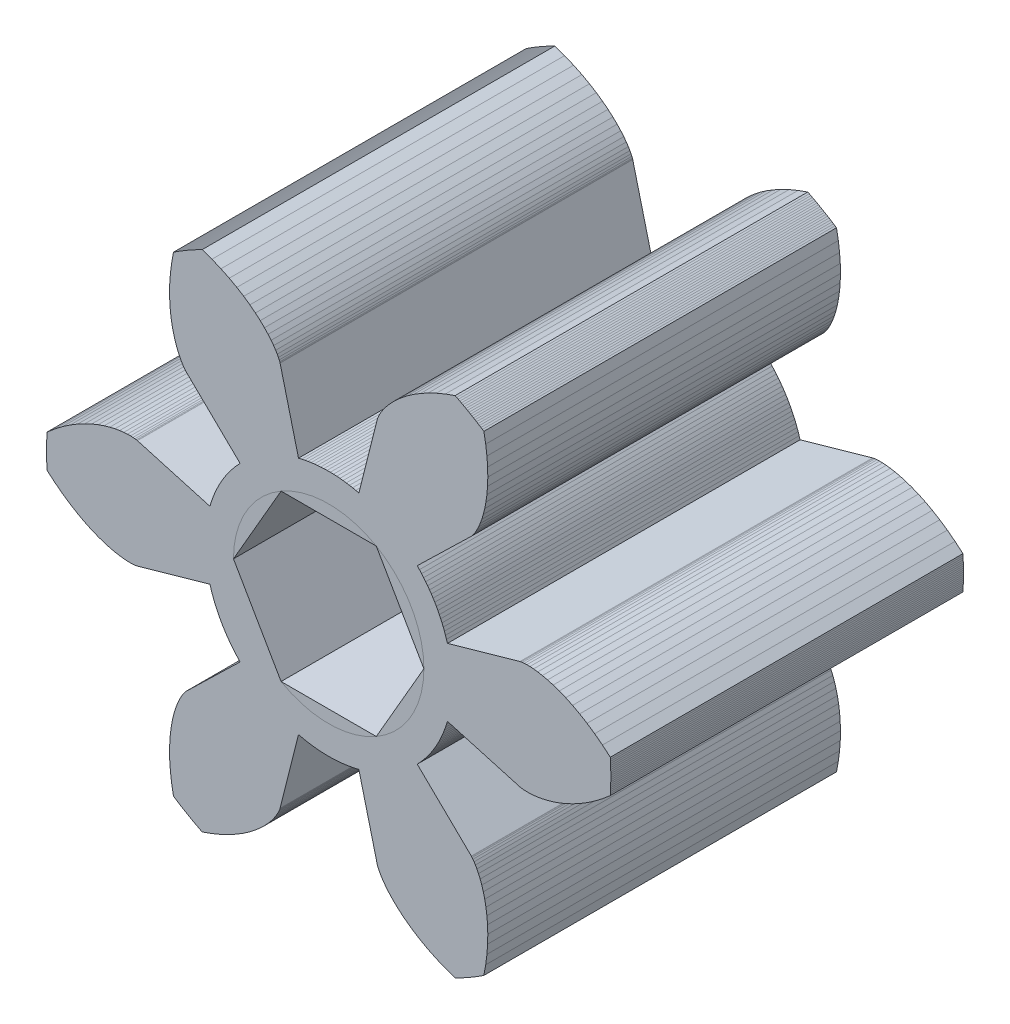
SolidWorks part; units mm, degrees
ref_plane "Front Plane" through (0, 0, 0) normal (0, 0, 1) x (1, 0, 0)
ref_plane "Top Plane" through (0, 0, 0) normal (0, 1, 0) x (1, 0, 0)
ref_plane "Right Plane" through (0, 0, 0) normal (1, 0, 0) x (0, 0, -1)
sketch "Model" plane through (0, 0, 0) normal (0, 0, 1) x (1, 0, 0)
  line L0 (3.3669, -0.9562) -> (5.4237, -1.5403)
  line L1 (5.4237, -1.5403) -> (5.4314, -1.5422)
  line L2 (5.4314, -1.5422) -> (5.4547, -1.5467)
  line L3 (5.4547, -1.5467) -> (5.4938, -1.5524)
  line L4 (5.4938, -1.5524) -> (5.549, -1.5573)
  line L5 (5.549, -1.5573) -> (5.6201, -1.56)
  line L6 (5.6201, -1.56) -> (5.7072, -1.5586)
  line L7 (5.7072, -1.5586) -> (5.8098, -1.5516)
  line L8 (5.8098, -1.5516) -> (5.9276, -1.5373)
  line L9 (5.9276, -1.5373) -> (6.06, -1.514)
  line L10 (6.06, -1.514) -> (6.2065, -1.4801)
  line L11 (6.2065, -1.4801) -> (6.3662, -1.4342)
  line L12 (6.3662, -1.4342) -> (6.5382, -1.3747)
  line L13 (6.5382, -1.3747) -> (6.7214, -1.3003)
  line L14 (6.7214, -1.3003) -> (6.9148, -1.2095)
  line L15 (6.9148, -1.2095) -> (7.1171, -1.1012)
  line L16 (7.1171, -1.1012) -> (7.3268, -0.9741)
  line L17 (7.3268, -0.9741) -> (7.5426, -0.8271)
  line L18 (7.5426, -0.8271) -> (7.763, -0.6594)
  line L19 (7.763, -0.6594) -> (7.9862, -0.47)
  line L20 (7.9862, -0.47) -> (7.9889, -0.4205)
  line L21 (7.9889, -0.4205) -> (7.9914, -0.3711)
  line L22 (7.9914, -0.3711) -> (7.9935, -0.3217)
  line L23 (7.9935, -0.3217) -> (7.9954, -0.2722)
  line L24 (7.9954, -0.2722) -> (7.9969, -0.2227)
  line L25 (7.9969, -0.2227) -> (7.9981, -0.1732)
  line L26 (7.9981, -0.1732) -> (7.999, -0.1237)
  line L27 (7.999, -0.1237) -> (7.9997, -0.0742)
  line L28 (7.9997, -0.0742) -> (8, -0.0247)
  line L29 (8, -0.0247) -> (8, 0.0247)
  line L30 (8, 0.0247) -> (7.9997, 0.0742)
  line L31 (7.9997, 0.0742) -> (7.999, 0.1237)
  line L32 (7.999, 0.1237) -> (7.9981, 0.1732)
  line L33 (7.9981, 0.1732) -> (7.9969, 0.2227)
  line L34 (7.9969, 0.2227) -> (7.9954, 0.2722)
  line L35 (7.9954, 0.2722) -> (7.9935, 0.3217)
  line L36 (7.9935, 0.3217) -> (7.9914, 0.3711)
  line L37 (7.9914, 0.3711) -> (7.9889, 0.4205)
  line L38 (7.9889, 0.4205) -> (7.9862, 0.47)
  line L39 (7.9862, 0.47) -> (7.763, 0.6594)
  line L40 (7.763, 0.6594) -> (7.5426, 0.8271)
  line L41 (7.5426, 0.8271) -> (7.3268, 0.9741)
  line L42 (7.3268, 0.9741) -> (7.1171, 1.1012)
  line L43 (7.1171, 1.1012) -> (6.9148, 1.2095)
  line L44 (6.9148, 1.2095) -> (6.7214, 1.3003)
  line L45 (6.7214, 1.3003) -> (6.5382, 1.3747)
  line L46 (6.5382, 1.3747) -> (6.3662, 1.4342)
  line L47 (6.3662, 1.4342) -> (6.2065, 1.4801)
  line L48 (6.2065, 1.4801) -> (6.06, 1.514)
  line L49 (6.06, 1.514) -> (5.9276, 1.5373)
  line L50 (5.9276, 1.5373) -> (5.8098, 1.5516)
  line L51 (5.8098, 1.5516) -> (5.7072, 1.5586)
  line L52 (5.7072, 1.5586) -> (5.6201, 1.56)
  line L53 (5.6201, 1.56) -> (5.549, 1.5573)
  line L54 (5.549, 1.5573) -> (5.4938, 1.5524)
  line L55 (5.4938, 1.5524) -> (5.4547, 1.5467)
  line L56 (5.4547, 1.5467) -> (5.4314, 1.5422)
  line L57 (5.4314, 1.5422) -> (5.4237, 1.5403)
  line L58 (5.4237, 1.5403) -> (3.3669, 0.9562)
  line L59 (3.3669, 0.9562) -> (3.3409, 1.0433)
  line L60 (3.3409, 1.0433) -> (3.3126, 1.1298)
  line L61 (3.3126, 1.1298) -> (3.2822, 1.2155)
  line L62 (3.2822, 1.2155) -> (3.2495, 1.3004)
  line L63 (3.2495, 1.3004) -> (3.2146, 1.3844)
  line L64 (3.2146, 1.3844) -> (3.1775, 1.4674)
  line L65 (3.1775, 1.4674) -> (3.1383, 1.5495)
  line L66 (3.1383, 1.5495) -> (3.097, 1.6305)
  line L67 (3.097, 1.6305) -> (3.0536, 1.7105)
  line L68 (3.0536, 1.7105) -> (3.0081, 1.7892)
  line L69 (3.0081, 1.7892) -> (2.9606, 1.8668)
  line L70 (2.9606, 1.8668) -> (2.9111, 1.9431)
  line L71 (2.9111, 1.9431) -> (2.8596, 2.0181)
  line L72 (2.8596, 2.0181) -> (2.8062, 2.0917)
  line L73 (2.8062, 2.0917) -> (2.7509, 2.1639)
  line L74 (2.7509, 2.1639) -> (2.6937, 2.2347)
  line L75 (2.6937, 2.2347) -> (2.6347, 2.3039)
  line L76 (2.6347, 2.3039) -> (2.574, 2.3716)
  line L77 (2.574, 2.3716) -> (2.5115, 2.4377)
  line L78 (2.5115, 2.4377) -> (4.0458, 3.9269)
  line L79 (4.0458, 3.9269) -> (4.0512, 3.9326)
  line L80 (4.0512, 3.9326) -> (4.0668, 3.9505)
  line L81 (4.0668, 3.9505) -> (4.0913, 3.9816)
  line L82 (4.0913, 3.9816) -> (4.1232, 4.0269)
  line L83 (4.1232, 4.0269) -> (4.1611, 4.0872)
  line L84 (4.1611, 4.0872) -> (4.2034, 4.1632)
  line L85 (4.2034, 4.1632) -> (4.2486, 4.2556)
  line L86 (4.2486, 4.2556) -> (4.2951, 4.3648)
  line L87 (4.2951, 4.3648) -> (4.3412, 4.4912)
  line L88 (4.3412, 4.4912) -> (4.3851, 4.6349)
  line L89 (4.3851, 4.6349) -> (4.4252, 4.7962)
  line L90 (4.4252, 4.7962) -> (4.4596, 4.9749)
  line L91 (4.4596, 4.9749) -> (4.4868, 5.1708)
  line L92 (4.4868, 5.1708) -> (4.5049, 5.3836)
  line L93 (4.5049, 5.3836) -> (4.5122, 5.613)
  line L94 (4.5122, 5.613) -> (4.507, 5.8582)
  line L95 (4.507, 5.8582) -> (4.4876, 6.1186)
  line L96 (4.4876, 6.1186) -> (4.4525, 6.3932)
  line L97 (4.4525, 6.3932) -> (4.4001, 6.6813)
  line L98 (4.4001, 6.6813) -> (4.3587, 6.7084)
  line L99 (4.3587, 6.7084) -> (4.3171, 6.7352)
  line L100 (4.3171, 6.7352) -> (4.2753, 6.7618)
  line L101 (4.2753, 6.7618) -> (4.2334, 6.7881)
  line L102 (4.2334, 6.7881) -> (4.1913, 6.8142)
  line L103 (4.1913, 6.8142) -> (4.1491, 6.84)
  line L104 (4.1491, 6.84) -> (4.1067, 6.8655)
  line L105 (4.1067, 6.8655) -> (4.0641, 6.8908)
  line L106 (4.0641, 6.8908) -> (4.0214, 6.9158)
  line L107 (4.0214, 6.9158) -> (3.9785, 6.9405)
  line L108 (3.9785, 6.9405) -> (3.9355, 6.965)
  line L109 (3.9355, 6.965) -> (3.8924, 6.9892)
  line L110 (3.8924, 6.9892) -> (3.849, 7.0132)
  line L111 (3.849, 7.0132) -> (3.8056, 7.0369)
  line L112 (3.8056, 7.0369) -> (3.762, 7.0603)
  line L113 (3.762, 7.0603) -> (3.7182, 7.0834)
  line L114 (3.7182, 7.0834) -> (3.6743, 7.1063)
  line L115 (3.6743, 7.1063) -> (3.6303, 7.1289)
  line L116 (3.6303, 7.1289) -> (3.5861, 7.1512)
  line L117 (3.5861, 7.1512) -> (3.3104, 7.0526)
  line L118 (3.3104, 7.0526) -> (3.055, 6.9457)
  line L119 (3.055, 6.9457) -> (2.8199, 6.8322)
  line L120 (2.8199, 6.8322) -> (2.6049, 6.7141)
  line L121 (2.6049, 6.7141) -> (2.4099, 6.5932)
  line L122 (2.4099, 6.5932) -> (2.2346, 6.4711)
  line L123 (2.2346, 6.4711) -> (2.0785, 6.3496)
  line L124 (2.0785, 6.3496) -> (1.941, 6.2304)
  line L125 (1.941, 6.2304) -> (1.8214, 6.1151)
  line L126 (1.8214, 6.1151) -> (1.7189, 6.0051)
  line L127 (1.7189, 6.0051) -> (1.6325, 5.9021)
  line L128 (1.6325, 5.9021) -> (1.5611, 5.8072)
  line L129 (1.5611, 5.8072) -> (1.5038, 5.7219)
  line L130 (1.5038, 5.7219) -> (1.4591, 5.6472)
  line L131 (1.4591, 5.6472) -> (1.4258, 5.5842)
  line L132 (1.4258, 5.5842) -> (1.4025, 5.534)
  line L133 (1.4025, 5.534) -> (1.3878, 5.4972)
  line L134 (1.3878, 5.4972) -> (1.3801, 5.4748)
  line L135 (1.3801, 5.4748) -> (1.3779, 5.4672)
  line L136 (1.3779, 5.4672) -> (0.8554, 3.3939)
  line L137 (0.8554, 3.3939) -> (0.7669, 3.4149)
  line L138 (0.7669, 3.4149) -> (0.6779, 3.4337)
  line L139 (0.6779, 3.4337) -> (0.5884, 3.4502)
  line L140 (0.5884, 3.4502) -> (0.4986, 3.4643)
  line L141 (0.4986, 3.4643) -> (0.4084, 3.4761)
  line L142 (0.4084, 3.4761) -> (0.3179, 3.4855)
  line L143 (0.3179, 3.4855) -> (0.2272, 3.4926)
  line L144 (0.2272, 3.4926) -> (0.1364, 3.4973)
  line L145 (0.1364, 3.4973) -> (0.0455, 3.4997)
  line L146 (0.0455, 3.4997) -> (-0.0455, 3.4997)
  line L147 (-0.0455, 3.4997) -> (-0.1364, 3.4973)
  line L148 (-0.1364, 3.4973) -> (-0.2272, 3.4926)
  line L149 (-0.2272, 3.4926) -> (-0.3179, 3.4855)
  line L150 (-0.3179, 3.4855) -> (-0.4084, 3.4761)
  line L151 (-0.4084, 3.4761) -> (-0.4986, 3.4643)
  line L152 (-0.4986, 3.4643) -> (-0.5884, 3.4502)
  line L153 (-0.5884, 3.4502) -> (-0.6779, 3.4337)
  line L154 (-0.6779, 3.4337) -> (-0.7669, 3.4149)
  line L155 (-0.7669, 3.4149) -> (-0.8554, 3.3939)
  line L156 (-0.8554, 3.3939) -> (-1.3779, 5.4672)
  line L157 (-1.3779, 5.4672) -> (-1.3801, 5.4748)
  line L158 (-1.3801, 5.4748) -> (-1.3878, 5.4972)
  line L159 (-1.3878, 5.4972) -> (-1.4025, 5.534)
  line L160 (-1.4025, 5.534) -> (-1.4258, 5.5842)
  line L161 (-1.4258, 5.5842) -> (-1.4591, 5.6472)
  line L162 (-1.4591, 5.6472) -> (-1.5038, 5.7219)
  line L163 (-1.5038, 5.7219) -> (-1.5611, 5.8072)
  line L164 (-1.5611, 5.8072) -> (-1.6325, 5.9021)
  line L165 (-1.6325, 5.9021) -> (-1.7189, 6.0051)
  line L166 (-1.7189, 6.0051) -> (-1.8214, 6.1151)
  line L167 (-1.8214, 6.1151) -> (-1.941, 6.2304)
  line L168 (-1.941, 6.2304) -> (-2.0785, 6.3496)
  line L169 (-2.0785, 6.3496) -> (-2.2346, 6.4711)
  line L170 (-2.2346, 6.4711) -> (-2.4099, 6.5932)
  line L171 (-2.4099, 6.5932) -> (-2.6049, 6.7141)
  line L172 (-2.6049, 6.7141) -> (-2.8199, 6.8322)
  line L173 (-2.8199, 6.8322) -> (-3.055, 6.9457)
  line L174 (-3.055, 6.9457) -> (-3.3104, 7.0526)
  line L175 (-3.3104, 7.0526) -> (-3.5861, 7.1512)
  line L176 (-3.5861, 7.1512) -> (-3.6303, 7.1289)
  line L177 (-3.6303, 7.1289) -> (-3.6743, 7.1063)
  line L178 (-3.6743, 7.1063) -> (-3.7182, 7.0834)
  line L179 (-3.7182, 7.0834) -> (-3.762, 7.0603)
  line L180 (-3.762, 7.0603) -> (-3.8056, 7.0369)
  line L181 (-3.8056, 7.0369) -> (-3.849, 7.0132)
  line L182 (-3.849, 7.0132) -> (-3.8924, 6.9892)
  line L183 (-3.8924, 6.9892) -> (-3.9355, 6.965)
  line L184 (-3.9355, 6.965) -> (-3.9785, 6.9405)
  line L185 (-3.9785, 6.9405) -> (-4.0214, 6.9158)
  line L186 (-4.0214, 6.9158) -> (-4.0641, 6.8908)
  line L187 (-4.0641, 6.8908) -> (-4.1067, 6.8655)
  line L188 (-4.1067, 6.8655) -> (-4.1491, 6.84)
  line L189 (-4.1491, 6.84) -> (-4.1913, 6.8142)
  line L190 (-4.1913, 6.8142) -> (-4.2334, 6.7881)
  line L191 (-4.2334, 6.7881) -> (-4.2753, 6.7618)
  line L192 (-4.2753, 6.7618) -> (-4.3171, 6.7352)
  line L193 (-4.3171, 6.7352) -> (-4.3587, 6.7084)
  line L194 (-4.3587, 6.7084) -> (-4.4001, 6.6813)
  line L195 (-4.4001, 6.6813) -> (-4.4525, 6.3932)
  line L196 (-4.4525, 6.3932) -> (-4.4876, 6.1186)
  line L197 (-4.4876, 6.1186) -> (-4.507, 5.8582)
  line L198 (-4.507, 5.8582) -> (-4.5122, 5.613)
  line L199 (-4.5122, 5.613) -> (-4.5049, 5.3836)
  line L200 (-4.5049, 5.3836) -> (-4.4868, 5.1708)
  line L201 (-4.4868, 5.1708) -> (-4.4596, 4.9749)
  line L202 (-4.4596, 4.9749) -> (-4.4252, 4.7962)
  line L203 (-4.4252, 4.7962) -> (-4.3851, 4.6349)
  line L204 (-4.3851, 4.6349) -> (-4.3412, 4.4912)
  line L205 (-4.3412, 4.4912) -> (-4.2951, 4.3648)
  line L206 (-4.2951, 4.3648) -> (-4.2486, 4.2556)
  line L207 (-4.2486, 4.2556) -> (-4.2034, 4.1632)
  line L208 (-4.2034, 4.1632) -> (-4.1611, 4.0872)
  line L209 (-4.1611, 4.0872) -> (-4.1232, 4.0269)
  line L210 (-4.1232, 4.0269) -> (-4.0913, 3.9816)
  line L211 (-4.0913, 3.9816) -> (-4.0668, 3.9505)
  line L212 (-4.0668, 3.9505) -> (-4.0512, 3.9326)
  line L213 (-4.0512, 3.9326) -> (-4.0458, 3.9269)
  line L214 (-4.0458, 3.9269) -> (-2.5115, 2.4377)
  line L215 (-2.5115, 2.4377) -> (-2.574, 2.3716)
  line L216 (-2.574, 2.3716) -> (-2.6347, 2.3039)
  line L217 (-2.6347, 2.3039) -> (-2.6937, 2.2347)
  line L218 (-2.6937, 2.2347) -> (-2.7509, 2.1639)
  line L219 (-2.7509, 2.1639) -> (-2.8062, 2.0917)
  line L220 (-2.8062, 2.0917) -> (-2.8596, 2.0181)
  line L221 (-2.8596, 2.0181) -> (-2.9111, 1.9431)
  line L222 (-2.9111, 1.9431) -> (-2.9606, 1.8668)
  line L223 (-2.9606, 1.8668) -> (-3.0081, 1.7892)
  line L224 (-3.0081, 1.7892) -> (-3.0536, 1.7105)
  line L225 (-3.0536, 1.7105) -> (-3.097, 1.6305)
  line L226 (-3.097, 1.6305) -> (-3.1383, 1.5495)
  line L227 (-3.1383, 1.5495) -> (-3.1775, 1.4674)
  line L228 (-3.1775, 1.4674) -> (-3.2146, 1.3844)
  line L229 (-3.2146, 1.3844) -> (-3.2495, 1.3004)
  line L230 (-3.2495, 1.3004) -> (-3.2822, 1.2155)
  line L231 (-3.2822, 1.2155) -> (-3.3126, 1.1298)
  line L232 (-3.3126, 1.1298) -> (-3.3409, 1.0433)
  line L233 (-3.3409, 1.0433) -> (-3.3669, 0.9562)
  line L234 (-3.3669, 0.9562) -> (-5.4237, 1.5403)
  line L235 (-5.4237, 1.5403) -> (-5.4314, 1.5422)
  line L236 (-5.4314, 1.5422) -> (-5.4547, 1.5467)
  line L237 (-5.4547, 1.5467) -> (-5.4938, 1.5524)
  line L238 (-5.4938, 1.5524) -> (-5.549, 1.5573)
  line L239 (-5.549, 1.5573) -> (-5.6201, 1.56)
  line L240 (-5.6201, 1.56) -> (-5.7072, 1.5586)
  line L241 (-5.7072, 1.5586) -> (-5.8098, 1.5516)
  line L242 (-5.8098, 1.5516) -> (-5.9276, 1.5373)
  line L243 (-5.9276, 1.5373) -> (-6.06, 1.514)
  line L244 (-6.06, 1.514) -> (-6.2065, 1.4801)
  line L245 (-6.2065, 1.4801) -> (-6.3662, 1.4342)
  line L246 (-6.3662, 1.4342) -> (-6.5382, 1.3747)
  line L247 (-6.5382, 1.3747) -> (-6.7214, 1.3003)
  line L248 (-6.7214, 1.3003) -> (-6.9148, 1.2095)
  line L249 (-6.9148, 1.2095) -> (-7.1171, 1.1012)
  line L250 (-7.1171, 1.1012) -> (-7.3268, 0.9741)
  line L251 (-7.3268, 0.9741) -> (-7.5426, 0.8271)
  line L252 (-7.5426, 0.8271) -> (-7.763, 0.6594)
  line L253 (-7.763, 0.6594) -> (-7.9862, 0.47)
  line L254 (-7.9862, 0.47) -> (-7.9889, 0.4205)
  line L255 (-7.9889, 0.4205) -> (-7.9914, 0.3711)
  line L256 (-7.9914, 0.3711) -> (-7.9935, 0.3217)
  line L257 (-7.9935, 0.3217) -> (-7.9954, 0.2722)
  line L258 (-7.9954, 0.2722) -> (-7.9969, 0.2227)
  line L259 (-7.9969, 0.2227) -> (-7.9981, 0.1732)
  line L260 (-7.9981, 0.1732) -> (-7.999, 0.1237)
  line L261 (-7.999, 0.1237) -> (-7.9997, 0.0742)
  line L262 (-7.9997, 0.0742) -> (-8, 0.0247)
  line L263 (-8, 0.0247) -> (-8, -0.0247)
  line L264 (-8, -0.0247) -> (-7.9997, -0.0742)
  line L265 (-7.9997, -0.0742) -> (-7.999, -0.1237)
  line L266 (-7.999, -0.1237) -> (-7.9981, -0.1732)
  line L267 (-7.9981, -0.1732) -> (-7.9969, -0.2227)
  line L268 (-7.9969, -0.2227) -> (-7.9954, -0.2722)
  line L269 (-7.9954, -0.2722) -> (-7.9935, -0.3217)
  line L270 (-7.9935, -0.3217) -> (-7.9914, -0.3711)
  line L271 (-7.9914, -0.3711) -> (-7.9889, -0.4205)
  line L272 (-7.9889, -0.4205) -> (-7.9862, -0.47)
  line L273 (-7.9862, -0.47) -> (-7.763, -0.6594)
  line L274 (-7.763, -0.6594) -> (-7.5426, -0.8271)
  line L275 (-7.5426, -0.8271) -> (-7.3268, -0.9741)
  line L276 (-7.3268, -0.9741) -> (-7.1171, -1.1012)
  line L277 (-7.1171, -1.1012) -> (-6.9148, -1.2095)
  line L278 (-6.9148, -1.2095) -> (-6.7214, -1.3003)
  line L279 (-6.7214, -1.3003) -> (-6.5382, -1.3747)
  line L280 (-6.5382, -1.3747) -> (-6.3662, -1.4342)
  line L281 (-6.3662, -1.4342) -> (-6.2065, -1.4801)
  line L282 (-6.2065, -1.4801) -> (-6.06, -1.514)
  line L283 (-6.06, -1.514) -> (-5.9276, -1.5373)
  line L284 (-5.9276, -1.5373) -> (-5.8098, -1.5516)
  line L285 (-5.8098, -1.5516) -> (-5.7072, -1.5586)
  line L286 (-5.7072, -1.5586) -> (-5.6201, -1.56)
  line L287 (-5.6201, -1.56) -> (-5.549, -1.5573)
  line L288 (-5.549, -1.5573) -> (-5.4938, -1.5524)
  line L289 (-5.4938, -1.5524) -> (-5.4547, -1.5467)
  line L290 (-5.4547, -1.5467) -> (-5.4314, -1.5422)
  line L291 (-5.4314, -1.5422) -> (-5.4237, -1.5403)
  line L292 (-5.4237, -1.5403) -> (-3.3669, -0.9562)
  line L293 (-3.3669, -0.9562) -> (-3.3409, -1.0433)
  line L294 (-3.3409, -1.0433) -> (-3.3126, -1.1298)
  line L295 (-3.3126, -1.1298) -> (-3.2822, -1.2155)
  line L296 (-3.2822, -1.2155) -> (-3.2495, -1.3004)
  line L297 (-3.2495, -1.3004) -> (-3.2146, -1.3844)
  line L298 (-3.2146, -1.3844) -> (-3.1775, -1.4674)
  line L299 (-3.1775, -1.4674) -> (-3.1383, -1.5495)
  line L300 (-3.1383, -1.5495) -> (-3.097, -1.6305)
  line L301 (-3.097, -1.6305) -> (-3.0536, -1.7105)
  line L302 (-3.0536, -1.7105) -> (-3.0081, -1.7892)
  line L303 (-3.0081, -1.7892) -> (-2.9606, -1.8668)
  line L304 (-2.9606, -1.8668) -> (-2.9111, -1.9431)
  line L305 (-2.9111, -1.9431) -> (-2.8596, -2.0181)
  line L306 (-2.8596, -2.0181) -> (-2.8062, -2.0917)
  line L307 (-2.8062, -2.0917) -> (-2.7509, -2.1639)
  line L308 (-2.7509, -2.1639) -> (-2.6937, -2.2347)
  line L309 (-2.6937, -2.2347) -> (-2.6347, -2.3039)
  line L310 (-2.6347, -2.3039) -> (-2.574, -2.3716)
  line L311 (-2.574, -2.3716) -> (-2.5115, -2.4377)
  line L312 (-2.5115, -2.4377) -> (-4.0458, -3.9269)
  line L313 (-4.0458, -3.9269) -> (-4.0512, -3.9326)
  line L314 (-4.0512, -3.9326) -> (-4.0668, -3.9505)
  line L315 (-4.0668, -3.9505) -> (-4.0913, -3.9816)
  line L316 (-4.0913, -3.9816) -> (-4.1232, -4.0269)
  line L317 (-4.1232, -4.0269) -> (-4.1611, -4.0872)
  line L318 (-4.1611, -4.0872) -> (-4.2034, -4.1632)
  line L319 (-4.2034, -4.1632) -> (-4.2486, -4.2556)
  line L320 (-4.2486, -4.2556) -> (-4.2951, -4.3648)
  line L321 (-4.2951, -4.3648) -> (-4.3412, -4.4912)
  line L322 (-4.3412, -4.4912) -> (-4.3851, -4.6349)
  line L323 (-4.3851, -4.6349) -> (-4.4252, -4.7962)
  line L324 (-4.4252, -4.7962) -> (-4.4596, -4.9749)
  line L325 (-4.4596, -4.9749) -> (-4.4868, -5.1708)
  line L326 (-4.4868, -5.1708) -> (-4.5049, -5.3836)
  line L327 (-4.5049, -5.3836) -> (-4.5122, -5.613)
  line L328 (-4.5122, -5.613) -> (-4.507, -5.8582)
  line L329 (-4.507, -5.8582) -> (-4.4876, -6.1186)
  line L330 (-4.4876, -6.1186) -> (-4.4525, -6.3932)
  line L331 (-4.4525, -6.3932) -> (-4.4001, -6.6813)
  line L332 (-4.4001, -6.6813) -> (-4.3587, -6.7084)
  line L333 (-4.3587, -6.7084) -> (-4.3171, -6.7352)
  line L334 (-4.3171, -6.7352) -> (-4.2753, -6.7618)
  line L335 (-4.2753, -6.7618) -> (-4.2334, -6.7881)
  line L336 (-4.2334, -6.7881) -> (-4.1913, -6.8142)
  line L337 (-4.1913, -6.8142) -> (-4.1491, -6.84)
  line L338 (-4.1491, -6.84) -> (-4.1067, -6.8655)
  line L339 (-4.1067, -6.8655) -> (-4.0641, -6.8908)
  line L340 (-4.0641, -6.8908) -> (-4.0214, -6.9158)
  line L341 (-4.0214, -6.9158) -> (-3.9785, -6.9405)
  line L342 (-3.9785, -6.9405) -> (-3.9355, -6.965)
  line L343 (-3.9355, -6.965) -> (-3.8924, -6.9892)
  line L344 (-3.8924, -6.9892) -> (-3.849, -7.0132)
  line L345 (-3.849, -7.0132) -> (-3.8056, -7.0369)
  line L346 (-3.8056, -7.0369) -> (-3.762, -7.0603)
  line L347 (-3.762, -7.0603) -> (-3.7182, -7.0834)
  line L348 (-3.7182, -7.0834) -> (-3.6743, -7.1063)
  line L349 (-3.6743, -7.1063) -> (-3.6303, -7.1289)
  line L350 (-3.6303, -7.1289) -> (-3.5861, -7.1512)
  line L351 (-3.5861, -7.1512) -> (-3.3104, -7.0526)
  line L352 (-3.3104, -7.0526) -> (-3.055, -6.9457)
  line L353 (-3.055, -6.9457) -> (-2.8199, -6.8322)
  line L354 (-2.8199, -6.8322) -> (-2.6049, -6.7141)
  line L355 (-2.6049, -6.7141) -> (-2.4099, -6.5932)
  line L356 (-2.4099, -6.5932) -> (-2.2346, -6.4711)
  line L357 (-2.2346, -6.4711) -> (-2.0785, -6.3496)
  line L358 (-2.0785, -6.3496) -> (-1.941, -6.2304)
  line L359 (-1.941, -6.2304) -> (-1.8214, -6.1151)
  line L360 (-1.8214, -6.1151) -> (-1.7189, -6.0051)
  line L361 (-1.7189, -6.0051) -> (-1.6325, -5.9021)
  line L362 (-1.6325, -5.9021) -> (-1.5611, -5.8072)
  line L363 (-1.5611, -5.8072) -> (-1.5038, -5.7219)
  line L364 (-1.5038, -5.7219) -> (-1.4591, -5.6472)
  line L365 (-1.4591, -5.6472) -> (-1.4258, -5.5842)
  line L366 (-1.4258, -5.5842) -> (-1.4025, -5.534)
  line L367 (-1.4025, -5.534) -> (-1.3878, -5.4972)
  line L368 (-1.3878, -5.4972) -> (-1.3801, -5.4748)
  line L369 (-1.3801, -5.4748) -> (-1.3779, -5.4672)
  line L370 (-1.3779, -5.4672) -> (-0.8554, -3.3939)
  line L371 (-0.8554, -3.3939) -> (-0.7669, -3.4149)
  line L372 (-0.7669, -3.4149) -> (-0.6779, -3.4337)
  line L373 (-0.6779, -3.4337) -> (-0.5884, -3.4502)
  line L374 (-0.5884, -3.4502) -> (-0.4986, -3.4643)
  line L375 (-0.4986, -3.4643) -> (-0.4084, -3.4761)
  line L376 (-0.4084, -3.4761) -> (-0.3179, -3.4855)
  line L377 (-0.3179, -3.4855) -> (-0.2272, -3.4926)
  line L378 (-0.2272, -3.4926) -> (-0.1364, -3.4973)
  line L379 (-0.1364, -3.4973) -> (-0.0455, -3.4997)
  line L380 (-0.0455, -3.4997) -> (0.0455, -3.4997)
  line L381 (0.0455, -3.4997) -> (0.1364, -3.4973)
  line L382 (0.1364, -3.4973) -> (0.2272, -3.4926)
  line L383 (0.2272, -3.4926) -> (0.3179, -3.4855)
  line L384 (0.3179, -3.4855) -> (0.4084, -3.4761)
  line L385 (0.4084, -3.4761) -> (0.4986, -3.4643)
  line L386 (0.4986, -3.4643) -> (0.5884, -3.4502)
  line L387 (0.5884, -3.4502) -> (0.6779, -3.4337)
  line L388 (0.6779, -3.4337) -> (0.7669, -3.4149)
  line L389 (0.7669, -3.4149) -> (0.8554, -3.3939)
  line L390 (0.8554, -3.3939) -> (1.3779, -5.4672)
  line L391 (1.3779, -5.4672) -> (1.3801, -5.4748)
  line L392 (1.3801, -5.4748) -> (1.3878, -5.4972)
  line L393 (1.3878, -5.4972) -> (1.4025, -5.534)
  line L394 (1.4025, -5.534) -> (1.4258, -5.5842)
  line L395 (1.4258, -5.5842) -> (1.4591, -5.6472)
  line L396 (1.4591, -5.6472) -> (1.5038, -5.7219)
  line L397 (1.5038, -5.7219) -> (1.5611, -5.8072)
  line L398 (1.5611, -5.8072) -> (1.6325, -5.9021)
  line L399 (1.6325, -5.9021) -> (1.7189, -6.0051)
  line L400 (1.7189, -6.0051) -> (1.8214, -6.1151)
  line L401 (1.8214, -6.1151) -> (1.941, -6.2304)
  line L402 (1.941, -6.2304) -> (2.0785, -6.3496)
  line L403 (2.0785, -6.3496) -> (2.2346, -6.4711)
  line L404 (2.2346, -6.4711) -> (2.4099, -6.5932)
  line L405 (2.4099, -6.5932) -> (2.6049, -6.7141)
  line L406 (2.6049, -6.7141) -> (2.8199, -6.8322)
  line L407 (2.8199, -6.8322) -> (3.055, -6.9457)
  line L408 (3.055, -6.9457) -> (3.3104, -7.0526)
  line L409 (3.3104, -7.0526) -> (3.5861, -7.1512)
  line L410 (3.5861, -7.1512) -> (3.6303, -7.1289)
  line L411 (3.6303, -7.1289) -> (3.6743, -7.1063)
  line L412 (3.6743, -7.1063) -> (3.7182, -7.0834)
  line L413 (3.7182, -7.0834) -> (3.762, -7.0603)
  line L414 (3.762, -7.0603) -> (3.8056, -7.0369)
  line L415 (3.8056, -7.0369) -> (3.849, -7.0132)
  line L416 (3.849, -7.0132) -> (3.8924, -6.9892)
  line L417 (3.8924, -6.9892) -> (3.9355, -6.965)
  line L418 (3.9355, -6.965) -> (3.9785, -6.9405)
  line L419 (3.9785, -6.9405) -> (4.0214, -6.9158)
  line L420 (4.0214, -6.9158) -> (4.0641, -6.8908)
  line L421 (4.0641, -6.8908) -> (4.1067, -6.8655)
  line L422 (4.1067, -6.8655) -> (4.1491, -6.84)
  line L423 (4.1491, -6.84) -> (4.1913, -6.8142)
  line L424 (4.1913, -6.8142) -> (4.2334, -6.7881)
  line L425 (4.2334, -6.7881) -> (4.2753, -6.7618)
  line L426 (4.2753, -6.7618) -> (4.3171, -6.7352)
  line L427 (4.3171, -6.7352) -> (4.3587, -6.7084)
  line L428 (4.3587, -6.7084) -> (4.4001, -6.6813)
  line L429 (4.4001, -6.6813) -> (4.4525, -6.3932)
  line L430 (4.4525, -6.3932) -> (4.4876, -6.1186)
  line L431 (4.4876, -6.1186) -> (4.507, -5.8582)
  line L432 (4.507, -5.8582) -> (4.5122, -5.613)
  line L433 (4.5122, -5.613) -> (4.5049, -5.3836)
  line L434 (4.5049, -5.3836) -> (4.4868, -5.1708)
  line L435 (4.4868, -5.1708) -> (4.4596, -4.9749)
  line L436 (4.4596, -4.9749) -> (4.4252, -4.7962)
  line L437 (4.4252, -4.7962) -> (4.3851, -4.6349)
  line L438 (4.3851, -4.6349) -> (4.3412, -4.4912)
  line L439 (4.3412, -4.4912) -> (4.2951, -4.3648)
  line L440 (4.2951, -4.3648) -> (4.2486, -4.2556)
  line L441 (4.2486, -4.2556) -> (4.2034, -4.1632)
  line L442 (4.2034, -4.1632) -> (4.1611, -4.0872)
  line L443 (4.1611, -4.0872) -> (4.1232, -4.0269)
  line L444 (4.1232, -4.0269) -> (4.0913, -3.9816)
  line L445 (4.0913, -3.9816) -> (4.0668, -3.9505)
  line L446 (4.0668, -3.9505) -> (4.0512, -3.9326)
  line L447 (4.0512, -3.9326) -> (4.0458, -3.9269)
  line L448 (4.0458, -3.9269) -> (2.5115, -2.4377)
  line L449 (2.5115, -2.4377) -> (2.574, -2.3716)
  line L450 (2.574, -2.3716) -> (2.6347, -2.3039)
  line L451 (2.6347, -2.3039) -> (2.6937, -2.2347)
  line L452 (2.6937, -2.2347) -> (2.7509, -2.1639)
  line L453 (2.7509, -2.1639) -> (2.8062, -2.0917)
  line L454 (2.8062, -2.0917) -> (2.8596, -2.0181)
  line L455 (2.8596, -2.0181) -> (2.9111, -1.9431)
  line L456 (2.9111, -1.9431) -> (2.9606, -1.8668)
  line L457 (2.9606, -1.8668) -> (3.0081, -1.7892)
  line L458 (3.0081, -1.7892) -> (3.0536, -1.7105)
  line L459 (3.0536, -1.7105) -> (3.097, -1.6305)
  line L460 (3.097, -1.6305) -> (3.1383, -1.5495)
  line L461 (3.1383, -1.5495) -> (3.1775, -1.4674)
  line L462 (3.1775, -1.4674) -> (3.2146, -1.3844)
  line L463 (3.2146, -1.3844) -> (3.2495, -1.3004)
  line L464 (3.2495, -1.3004) -> (3.2822, -1.2155)
  line L465 (3.2822, -1.2155) -> (3.3126, -1.1298)
  line L466 (3.3126, -1.1298) -> (3.3409, -1.0433)
  line L467 (3.3409, -1.0433) -> (3.3669, -0.9562)
  circle A0 centre (0, 0) radius 2.6
extrude "Boss-Extrude1" add sketch "Model" along normal blind 5
extrude "Boss-Extrude2" add sketch "Model<3>" against normal blind 5
sketch "Model<3>" plane through (0, 0, 0) normal (0, 0, 1) x (1, 0, 0) same geometry as "Model"
sketch "Sketch1" plane through (0, 0, 0) normal (0, 1, 0) x (1, 0, 0)
  circle A0 centre (0, 0) radius 1.6
  circle A1 centre (0, 0) radius 2
sketch "Sketch2" plane through (0, 0, -5) normal (0, 0, -1) x (-1, 0, 0)
  circle A0 centre (0, 0) radius 2.7
extrude "Cut-Extrude3" cut sketch "Sketch2" against normal through all
sketch "Sketch3" plane through (0, 0, 5) normal (0, 0, 1) x (1, 0, 0)
  line L1 (2.7, 0) -> (1.35, 2.3383)
  line L2 (1.35, 2.3383) -> (-1.35, 2.3383)
  line L3 (-1.35, 2.3383) -> (-2.7, 0)
  line L4 (-2.7, 0) -> (-1.35, -2.3383)
  line L5 (-1.35, -2.3383) -> (1.35, -2.3383)
  line L6 (1.35, -2.3383) -> (2.7, 0)
  circle A0 centre (0, 0) radius 2.3383 construction
  circle A1 centre (0, 0) radius 2.7
extrude "Boss-Extrude6" add sketch "Sketch3" against normal blind 10 contours L4 A1 region at (-2.1511, -1.2419, 5)
extrude "Boss-Extrude7" add sketch "Sketch3<4>" against normal blind 10 separate body contours L1 A1 | L3 A1 | L5 A1 region at (2.1511, 1.2419, 5) region at (0, -2.4838, 5) region at (-2.1511, 1.2419, 5)
sketch "Sketch3<4>" plane through (0, 0, 5) normal (0, 0, 1) x (1, 0, 0) same geometry as "Sketch3"
extrude "Boss-Extrude8" add sketch "Sketch3<5>" against normal blind 10 separate body contours L6 A1 | L2 A1 region at (2.1511, -1.2419, 5) region at (0, 2.4838, 5)
sketch "Sketch3<5>" plane through (0, 0, 5) normal (0, 0, 1) x (1, 0, 0) same geometry as "Sketch3"
